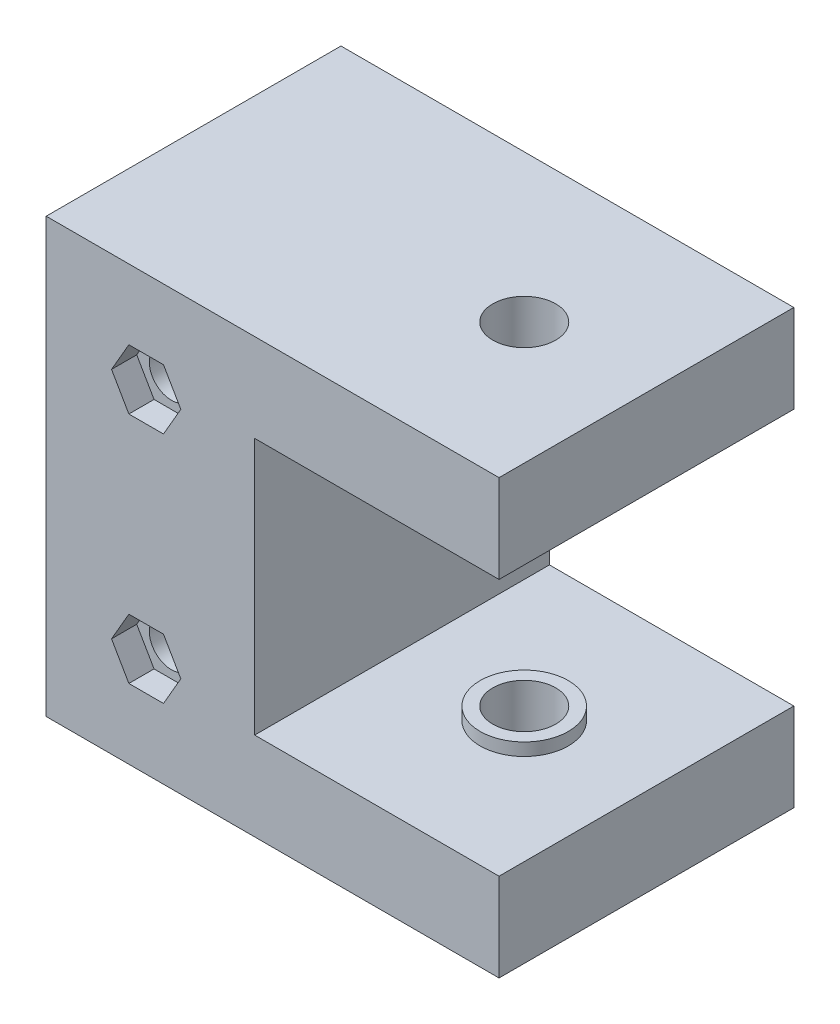
SolidWorks part; units mm, degrees
ref_plane "Front Plane" through (0, 0, 0) normal (0, 0, 1) x (1, 0, 0)
ref_plane "Top Plane" through (0, 0, 0) normal (0, 1, 0) x (1, 0, 0)
ref_plane "Right Plane" through (0, 0, 0) normal (1, 0, 0) x (0, 0, -1)
sketch "MainBlock" plane through (0, 0, 0) normal (0, 0, 1) x (1, 0, 0)
  line L0 (0, 0) -> (35.95, 0)
  line L1 (35.95, 0) -> (35.95, 7)
  line L2 (35.95, 7) -> (16.55, 7)
  line L3 (16.55, 7) -> (16.55, 27.4)
  line L4 (16.55, 27.4) -> (35.95, 27.4)
  line L5 (35.95, 27.4) -> (35.95, 34.4)
  line L6 (35.95, 34.4) -> (0, 34.4)
  line L7 (0, 34.4) -> (0, 0)
  circle A0 centre (7.9375, 26.4625) radius 1.75
  circle A1 centre (7.9375, 7.9375) radius 1.75
  dimension "D4" = 3.5
  dimension "D1" = 35.95
  dimension "D2" = 34.4
  dimension "D3" = 20.4
  dimension "D5" = 19.4
  dimension "D6" = 7.9375
  dimension "D7" = 7.9375
  dimension "D8" = 7.9375
extrude "MainBlockBoss-Extrude1" add sketch "MainBlock" along normal blind 23.4
sketch "TopHoleCut-Sketch2" plane through (0, 34.4, 0) normal (0, 1, 0) x (1, 0, 0)
  line L0 (35.95, 0) -> (0, 0) construction
  line L1 (0, -23.4) -> (0, 0) construction
  circle A0 centre (26.25, -11.7) radius 2.5
  dimension "D3" = 5
  dimension "D1" = 11.7
  dimension "D2" = 26.25
extrude "TopHoleCut-Extrude1" cut sketch "TopHoleCut-Sketch2" against normal blind 30
sketch "MountHoleBoreSketch3" plane through (0, 0, 23.4) normal (0, 0, 1) x (1, 0, 0)
  line L1 (10.6875, 26.4625) -> (9.3125, 28.8441)
  line L2 (9.3125, 28.8441) -> (6.5625, 28.8441)
  line L3 (6.5625, 28.8441) -> (5.1875, 26.4625)
  line L4 (5.1875, 26.4625) -> (6.5625, 24.0809)
  line L5 (6.5625, 24.0809) -> (9.3125, 24.0809)
  line L6 (9.3125, 24.0809) -> (10.6875, 26.4625)
  line L7 (10.6875, 7.9375) -> (9.3125, 10.3191)
  line L8 (9.3125, 10.3191) -> (6.5625, 10.3191)
  line L9 (6.5625, 10.3191) -> (5.1875, 7.9375)
  line L10 (5.1875, 7.9375) -> (6.5625, 5.5559)
  line L11 (6.5625, 5.5559) -> (9.3125, 5.5559)
  line L12 (9.3125, 5.5559) -> (10.6875, 7.9375)
  line L13 (0, 0) -> (35.95, 0) construction
  circle A0 centre (7.9375, 26.4625) radius 2.3816 construction
  circle A1 centre (7.9375, 7.9375) radius 2.3816 construction
  point P10 (7.9375, 28.8441)
  dimension "D1" = 5.5
  dimension "D2" = 24.0809
extrude "MountHoleBoreCut-Extrude2" cut sketch "MountHoleBoreSketch3" against normal blind 2
sketch "TopSpacerSketch4" plane through (0, 27.4, 0) normal (0, -1, 0) x (1, 0, 0)
  circle A0 centre (26.25, 11.7) radius 3.5
  circle A1 centre (26.25, 11.7) radius 2.5
  circle A2 centre (26.25, 11.7) radius 2.5 construction
  dimension "D1" = 7
extrude "TopSpacerBoss-Extrude2" add sketch "TopSpacerSketch4" along normal blind 1
sketch "LowerSpacerSketch5" plane through (0, 7, 0) normal (0, 1, 0) x (1, 0, 0)
  circle A0 centre (26.25, -11.7) radius 2.5
  circle A1 centre (26.25, -11.7) radius 2.5 construction
  circle A2 centre (26.25, -11.7) radius 3.5
  circle A3 centre (26.25, -11.7) radius 3.5 construction
extrude "LowerSpacerBoss-Extrude3" add sketch "LowerSpacerSketch5" along normal blind 1
sketch "PushPinHoleSketch1" plane through (0, 0, 0) normal (0, -1, 0) x (1, 0, 0)
  circle A0 centre (26.25, 11.7) radius 1
  circle A1 centre (26.25, 11.7) radius 2.5 construction
  dimension "D1" = 2
extrude "PushPinHoleCut-Extrude1" cut sketch "PushPinHoleSketch1" against normal through all
equation "\"BeltTensionerWidth\"= \"MidRailToAlignWithGantryBlock\" + \"BeltTensionerInnerWidth\" / 2"
equation "\"BeltTensionerHeight\"= \"BeltTensionerInnerHeight\" + \"BeltTensionerUpperLowerWallThickness\" * 2"
equation "\"BeltTensionerDepth\"= \"BeltTensionerBackWallThickness\" + \"BeltTensionerInnerDepth\"'Equals 23.4"
equation "\"BeltTensionerUpperLowerWallThickness\"= 7mm"
equation "\"BeltTensionerInnerWidth\"= \"20TGT2PulleyDiameter\" + \"BeltTensionerSpaceBetweenPulleyAndWall\""
equation "\"BeltTensionerInnerHeight\"= \"20TGT2PulleyWidth\" * 2 + \"1mmSpacer\" * 3"
equation "\"BeltTensionerBackWallThickness\"= 4mm"
equation "\"BeltTensionerInnerDepth\"= \"20TGT2PulleyDiameter\" + \"BeltTensionerSpaceBetweenPulleyAndWall\""
equation "\"RailThickness\"= .125in'Spec"
equation "\"HoleOffsetFromEdge\"= \"RailThickness\" * 2.5"
equation "\"LinearGBWithRailDepth\"= 12.75mm'Spec"
equation "\"GABDistanceFromBackToFirstPulley\"= 13.5mm"
equation "\"MidRailToAlignWithGantryBlock\"= \"LinearGBWithRailDepth\" + \"GABDistanceFromBackToFirstPulley\"'All outside cogs must align"
equation "\"20TGT2PulleyDiameter\"= 17.9mm'Spec"
equation "\"BeltTensionerSpaceBetweenPulleyAndWall\"= 1.5mm"
equation "\"BeltTensionerMountingHoleDiameter\"= 3.5mm'From the100"
equation "\"BeltTensionerMountingHoleOffsetFromEdge\"= \"HoleOffsetFromEdge\""
equation "\"20TGT2PulleyWidth\"= 8.7mm'The STL of the Pulley in the diagram is a bit larger"
equation "\"1mmSpacer\"= 1mm"
equation "\"SteelShaft5mmHoleDiameter\"= 5mm"
equation "\"BeltTensionerMountingHoleOuterBoreDepth\"= 2mm"
equation "\"BeltTensionerMountingHoleOuterBoreDiameter\"= 5.5mm'From the100"
equation "\"7mmx1mmSpacerDiameter\"= 7mm"
equation "\"7mmx1mmSpacerHeight\"= 1mm"
equation "\"D1@MainBlock\" = \"BeltTensionerWidth\""
equation "\"D2@MainBlock\" = \"BeltTensionerHeight\""
equation "\"D3@MainBlock\" = \"BeltTensionerInnerHeight\""
equation "\"D4@MainBlock\" = \"BeltTensionerMountingHoleDiameter\""
equation "\"D5@MainBlock\" = \"BeltTensionerInnerWidth\""
equation "\"D6@MainBlock\"=\"BeltTensionerMountingHoleOffsetFromEdge\""
equation "\"D7@MainBlock\" = \"HoleOffsetFromEdge\""
equation "\"D8@MainBlock\" = \"HoleOffsetFromEdge\""
equation "\"D1@MainBlockBoss-Extrude1\" = \"BeltTensionerDepth\""
equation "\"D1@TopHoleCut-Sketch2\" = \"BeltTensionerDepth\" / 2"
equation "\"D2@TopHoleCut-Sketch2\" = \"MidRailToAlignWithGantryBlock\""
equation "\"D3@TopHoleCut-Sketch2\" = \"SteelShaft5mmHoleDiameter\""
equation "\"D1@MountHoleBoreSketch3\" = \"BeltTensionerMountingHoleOuterBoreDiameter\""
equation "\"D1@MountHoleBoreCut-Extrude2\"=\"BeltTensionerMountingHoleOuterBoreDepth\""
equation "\"D1@TopSpacerSketch4\" = \"7mmx1mmSpacerDiameter\""
equation "\"D1@TopSpacerBoss-Extrude2\" = \"7mmx1mmSpacerHeight\""
equation "\"D1@LowerSpacerBoss-Extrude3\" = \"7mmx1mmSpacerHeight\""
equation "\"StealPinPushHoleDiameter\"= 2mm"
equation "\"D1@PushPinHoleSketch1\" = \"StealPinPushHoleDiameter\""
